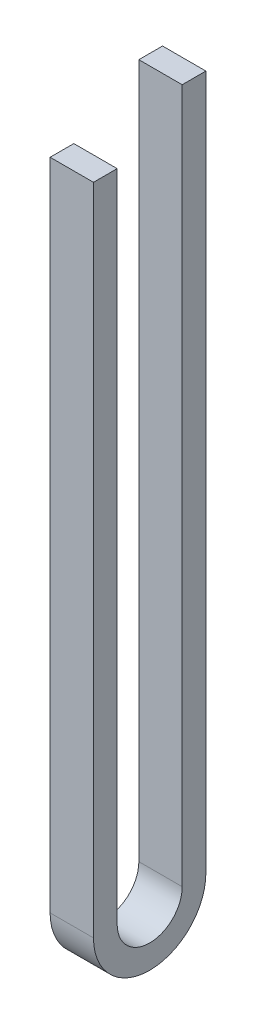
SolidWorks part; units mm, degrees
ref_plane "Front" through (0, 0, 0) normal (0, 0, 1) x (1, 0, 0)
ref_plane "Top" through (0, 0, 0) normal (0, 1, 0) x (1, 0, 0)
ref_plane "Right" through (0, 0, 0) normal (1, 0, 0) x (0, 0, -1)
sketch "Sketch1" plane through (0, 0, 0) normal (1, 0, 0) x (0, 0, -1)
  line L0 (0, 0) -> (0, -414.0425)
  line L1 (71.12, -414.0425) -> (71.12, 25.4)
  line L2 (14.986, 0) -> (14.986, -414.0425)
  line L3 (56.134, -414.0425) -> (56.134, 25.4)
  line L4 (0, 0) -> (14.986, 0)
  line L5 (56.134, 25.4) -> (71.12, 25.4)
  line L7 (-0.635, 25.4) -> (69.85, 25.4) construction
  arc A0 (0, -414.0425) -> (71.12, -414.0425) centre (35.56, -414.0425) ccw
  arc A1 (14.986, -414.0425) -> (56.134, -414.0425) centre (35.56, -414.0425) ccw
  dimension "D1" = 965.2
  dimension "D2" = 71.12
  dimension "D4" = 41.148
  dimension "D3" = 14.986
extrude "Boss-Extrude1" add sketch "Sketch1" along normal blind 27.432
